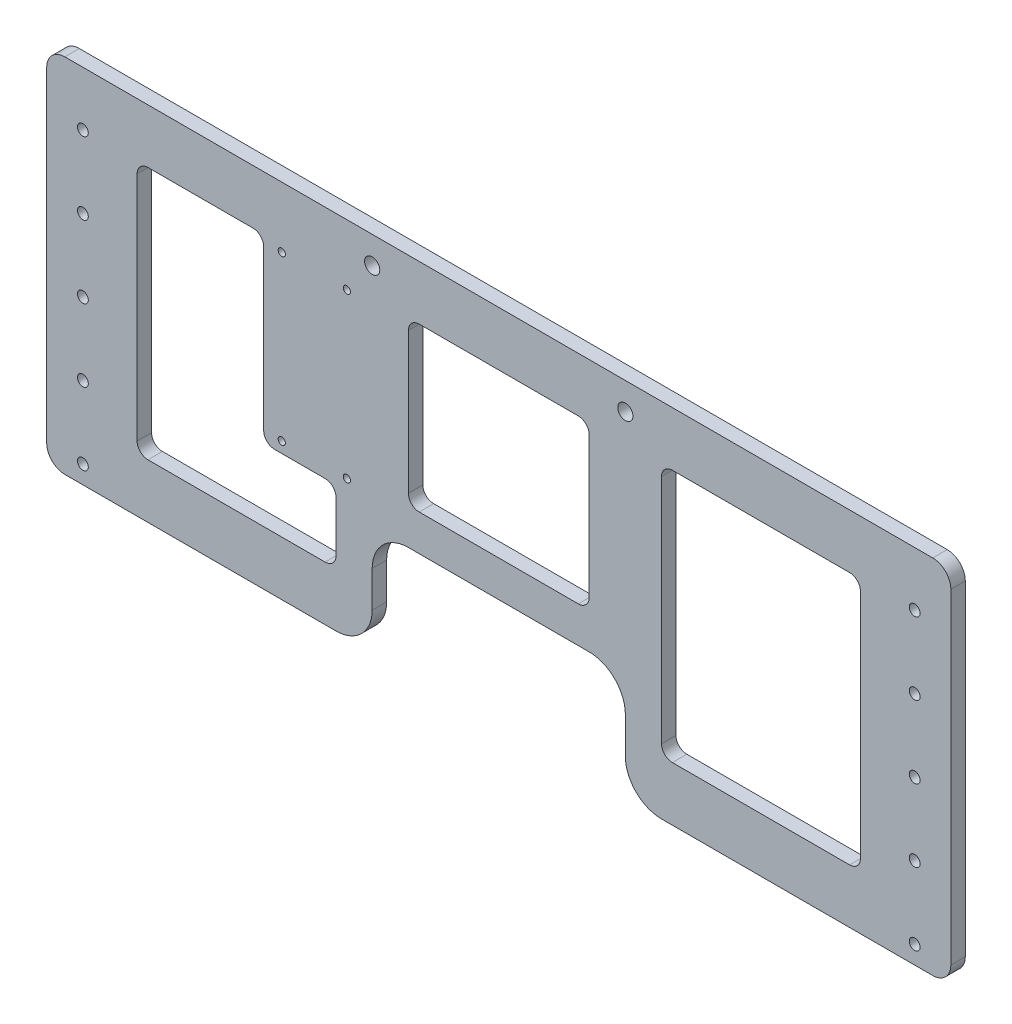
SolidWorks part; units mm, degrees
material "默认 (3)"
ref_plane "前视基准面" through (0, 0, 0) normal (0, 0, 1) x (1, 0, 0)
ref_plane "上视基准面" through (0, 0, 0) normal (0, 1, 0) x (1, 0, 0)
ref_plane "右视基准面" through (0, 0, 0) normal (1, 0, 0) x (0, 0, -1)
other "Configuration Table"
sketch "草图1" plane through (0, 0, 0) normal (0, 0, 1) x (1, 0, 0)
  line L0 (0, 0) -> (0, -50000) construction
  line L1 (-125, 15) -> (125, 15)
  line L2 (-125, 15) -> (-125, -15)
  line L3 (-125, -15) -> (125, -15)
  line L4 (125, 15) -> (125, -15)
  line L5 (-125, 15) -> (125, -15) construction
  line L6 (-125, -15) -> (125, 15) construction
  line L7 (-115, -10) -> (-115, 10) construction
  circle A0 centre (-115, -10) radius 1.5
  circle A1 centre (-115, 10) radius 1.5
  circle A2 centre (115, 10) radius 1.5
  circle A3 centre (115, -10) radius 1.5
  point P0 (0, 0)
  dimension "D6" = 5
  dimension "D7" = 3
  dimension "D1" = 250
  dimension "D2" = 30
  dimension "D4" = 20
  dimension "D5" = 10
  dimension "D3" = 2
extrude "凸台-拉伸1" add sketch "草图1" along normal blind 4
sketch "草图2" plane through (0, 0, 4) normal (0, 0, 1) x (1, 0, 0)
  line L0 (0, 0) -> (0, -50000) construction
  line L1 (0, 9) -> (50000, 9) construction
  line L2 (-23, 2.5) -> (23, 2.5) construction
  line L3 (-23, 2.5) -> (-23, 15.5) construction
  line L4 (-125, -15) -> (125, -15) construction
  circle A0 centre (-23, 2.5) radius 3
  circle A1 centre (23, 2.5) radius 3
  circle A2 centre (23, 15.5) radius 3
  circle A3 centre (-23, 15.5) radius 3
  dimension "D5" = 6
  dimension "D3" = 46
  dimension "D4" = 13
  dimension "D6" = 24
  dimension "D1" = 2
  dimension "D2" = 2
extrude "切除-拉伸1" cut sketch "草图2" against normal through all
sketch "草图3" plane through (0, 0, 4) normal (0, 0, 1) x (1, 0, 0)
  line L0 (0, 54.5) -> (0, -49945.5) construction
  line L1 (-125, 85) -> (125, 85)
  line L2 (-125, 85) -> (-125, 15)
  line L3 (-125, 15) -> (125, 15)
  line L4 (125, 85) -> (125, 15)
  line L5 (-125, 85) -> (125, 15) construction
  line L6 (-125, 15) -> (125, 85) construction
  line L8 (-115, 10) -> (-115, 30) construction
  circle A4 centre (-115, 10) radius 1.5 construction
  circle A5 centre (-115, 10) radius 1.5
  circle A6 centre (-115, 30) radius 1.5
  circle A7 centre (-115, 50) radius 1.5
  circle A8 centre (-115, 70) radius 1.5
  circle A9 centre (-115, 90) radius 1.5
  circle A10 centre (115, 10) radius 1.5
  circle A11 centre (115, 30) radius 1.5
  circle A12 centre (115, 50) radius 1.5
  circle A13 centre (115, 70) radius 1.5
  circle A14 centre (-35, 77.5) radius 2.1
  circle A15 centre (35, 77.5) radius 2.1
  point P0 (0, 50)
  line M16 (125, 15) -> (25.958, 15)
  dimension "D4" = 70
  dimension "D2" = 4.2
  dimension "D3" = 7.5
  dimension "D1" = 70
  dimension "D7" = 20
  dimension "D6" = 5
extrude "凸台-拉伸2" add sketch "草图3" against normal blind 4 contours L4 L1 L2 A12 A14 A6 A7 A8 A11 A13 M16 region at (0, 49.9563, 4)
sketch "草图4" plane through (0, 0, 4) normal (0, 0, 1) x (1, 0, 0)
  line L0 (0, 0) -> (0, -50000) construction
  line L1 (-125, 85) -> (125, 85) construction
  line L2 (-22, 70) -> (22, 70)
  line L3 (-25, 67) -> (-25, 28)
  line L4 (-22, 25) -> (22, 25)
  line L5 (25, 67) -> (25, 28)
  line L6 (-25, 70) -> (25, 25) construction
  line L7 (-25, 25) -> (25, 70) construction
  line L8 (-125, -15) -> (125, -15) construction
  line L9 (-97, 70) -> (-48, 70)
  line L10 (-100, 67) -> (-100, 3)
  line L11 (-97, 0) -> (-48, 0)
  line L12 (-45, 67) -> (-45, 3)
  line L13 (-100, 70) -> (-45, 0) construction
  line L14 (-100, 0) -> (-45, 70) construction
  line L15 (-125, 85) -> (-125, -15) construction
  line L16 (97, 0) -> (48, 0)
  line L17 (45, 67) -> (45, 3)
  line L18 (97, 70) -> (48, 70)
  line L19 (100, 67) -> (100, 3)
  arc A0 (22, 70) -> (25, 67) centre (22, 67) cw
  arc A1 (22, 25) -> (25, 28) centre (22, 28) ccw
  arc A2 (-25, 28) -> (-22, 25) centre (-22, 28) ccw
  arc A3 (-22, 70) -> (-25, 67) centre (-22, 67) ccw
  arc A4 (-48, 0) -> (-45, 3) centre (-48, 3) ccw
  arc A5 (-100, 3) -> (-97, 0) centre (-97, 3) ccw
  arc A6 (-48, 70) -> (-45, 67) centre (-48, 67) cw
  arc A7 (-97, 70) -> (-100, 67) centre (-97, 67) ccw
  arc A8 (48, 0) -> (45, 3) centre (48, 3) cw
  arc A9 (48, 70) -> (45, 67) centre (48, 67) ccw
  arc A10 (100, 3) -> (97, 0) centre (97, 3) cw
  arc A11 (97, 70) -> (100, 67) centre (97, 67) cw
  point P3 (0, 47.5)
  point P10 (-72.5, 35)
  dimension "D8" = 3
  dimension "D1" = 15
  dimension "D2" = 45
  dimension "D3" = 50
  dimension "D4" = 15
  dimension "D5" = 15
  dimension "D6" = 25
  dimension "D7" = 55
extrude "切除-拉伸2" cut sketch "草图4" against normal through all
fillet "圆角1" radius 5 4 edges at (125, -15, 2) (125, 85, 2) (-125, -15, 2) (-125, 85, 2)
sketch "草图5" plane through (0, 0, 4) normal (0, 0, 1) x (1, 0, 0)
  circle A0 centre (-23, 15.5) radius 3
  circle A1 centre (23, 15.5) radius 3
  dimension "D1" = 6
extrude "切除-拉伸3" cut sketch "草图5" against normal through all
sketch "草图8" plane through (0, 0, 4) normal (0, 0, 1) x (1, 0, 0)
  line L0 (-48, 70) -> (-97, 70) construction
  line L1 (-45, 70) -> (-65, 70)
  line L2 (-45, 70) -> (-45, 20)
  line L3 (-45, 20) -> (-65, 20)
  line L4 (-65, 70) -> (-65, 20)
  line L5 (-45, 3) -> (-45, 67) construction
  dimension "D1" = 50
  dimension "D2" = 20
extrude "凸台-拉伸4" add sketch "草图8" against normal up to surface (4 mm away) up to face at (72.5, 35, 0)
sketch "草图9" plane through (0, 0, 4) normal (0, 0, 1) x (1, 0, 0)
  line L0 (-65, 20) -> (-45, 20) construction
  line L1 (-65, 70) -> (-65, 20) construction
  circle A0 centre (-60, 23) radius 1
  circle A1 centre (-42, 23) radius 1
  circle A2 centre (-60, 68.2) radius 1
  circle A3 centre (-42, 68.2) radius 1
  dimension "D1" = 2
  dimension "D4" = 3
  dimension "D5" = 5
  dimension "D2" = 2
  dimension "D3" = 2
extrude "切除-拉伸4" cut sketch "草图9" against normal blind 10
fillet "圆角3" radius 3 3 edges at (-45, 20, 2) (-65, 70, 2) (-65, 20, 2)
sketch "草图10" plane through (0, 0, 4) normal (0, 0, 1) x (1, 0, 0)
  line L0 (0, 0) -> (0, 130.9934) construction
  line L1 (35, 15) -> (35, -15)
  line L2 (35, 15) -> (-35, 15)
  line L3 (0, 15) -> (0, -15)
  line L4 (35, -15) -> (-35, -15)
  line L5 (-35, 15) -> (-35, -15)
  line L7 (-22, 25) -> (22, 25) construction
  dimension "D1" = 70
  dimension "D2" = 30
  dimension "D3" = 10
extrude "切除-拉伸5" cut sketch "草图10" against normal blind 10 contours L2 L5 L4 L3 | L4 L1 L2 L3 region at (17.5, 0, 4) region at (-17.5, 0, 4)
sketch "草图11" plane through (0, 0, 4) normal (0, 0, 1) x (1, 0, 0)
  line L1 (-35, 15) -> (35, 15)
  line L2 (-35, 15) -> (-35, 22.5072)
  line L3 (-35, 22.5072) -> (35, 22.5072)
  line L4 (35, 15) -> (35, 22.5072)
extrude "凸台-拉伸5" add sketch "草图11" against normal up to surface (4 mm away) up to face at (-41, 23, 0)
fillet "圆角4" radius 10 4 edges at (35, 15, 2) (35, -15, 2) (-35, -15, 2) (-35, 15, 2)
